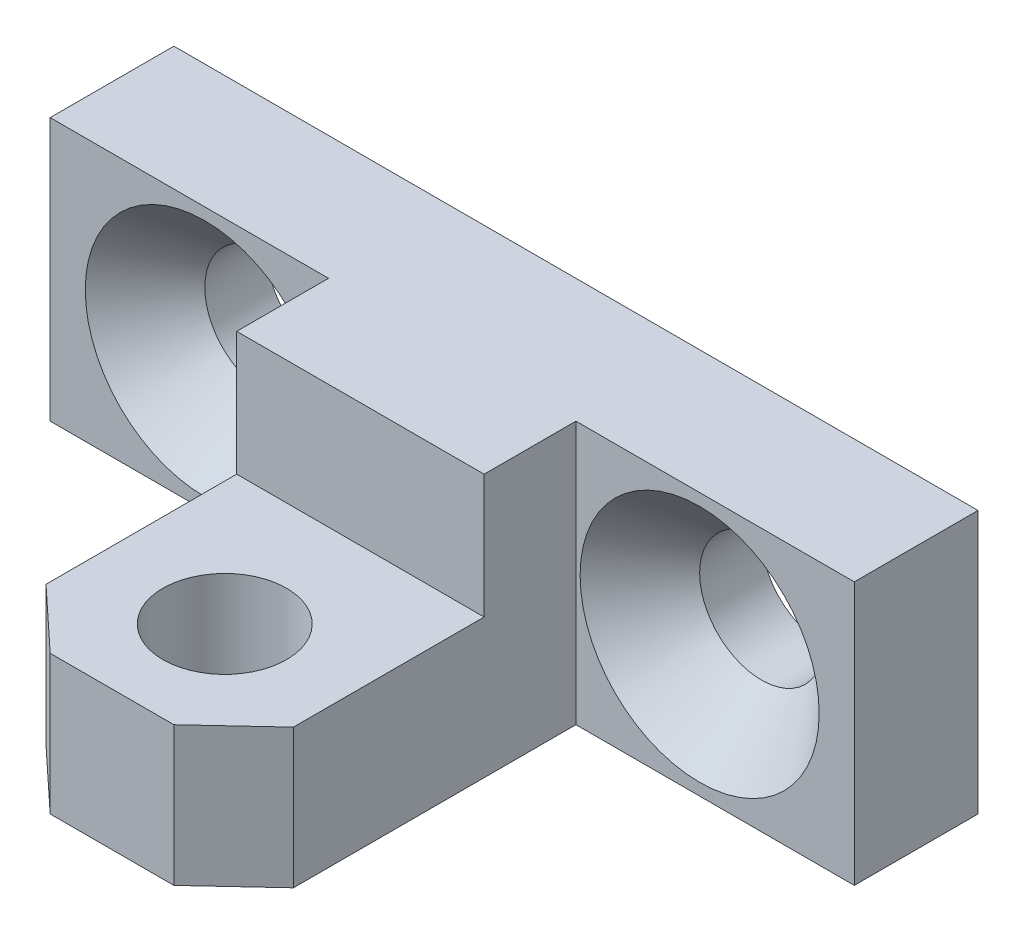
SolidWorks part; units mm, degrees
ref_plane "Спереди" through (0, 0, 0) normal (0, 0, 1) x (1, 0, 0)
ref_plane "Сверху" through (0, 0, 0) normal (0, 1, 0) x (1, 0, 0)
ref_plane "Справа" through (0, 0, 0) normal (1, 0, 0) x (0, 0, -1)
sketch "Эскиз1" plane through (0, 0, 0) normal (0, 0, 1) x (1, 0, 0)
  line L1 (0, 0) -> (26, 0)
  line L2 (0, 0) -> (0, -8.5)
  line L3 (0, -8.5) -> (26, -8.5)
  line L4 (26, 0) -> (26, -8.5)
extrude "Вытянуть1" add sketch "Эскиз1" along normal blind 15
sketch "Эскиз2" plane through (0, 0, 0) normal (0, 1, 0) x (1, 0, 0)
  line L0 (13, 0) -> (13, 9.2119) construction
  line L2 (0, -15) -> (0, 0) construction
  line L3 (0, -4) -> (9, -4)
  line L4 (0, -4) -> (0, -21.1515)
  line L5 (0, -21.1515) -> (9, -21.1515)
  line L6 (9, -4) -> (9, -21.1515)
  line L7 (26, 0) -> (0, 0) construction
  line L8 (17, -4) -> (17, -21.1515)
  line L9 (26, -21.1515) -> (17, -21.1515)
  line L10 (26, -4) -> (26, -21.1515)
  line L11 (26, -4) -> (17, -4)
  dimension "D1" = 4
extrude "Вытянуть2" cut sketch "Эскиз2" against normal blind 20
chamfer "Фаска1" distance 2 angle 43 2 edges at (17, -4.25, 15) (9, -4.25, 15) first distance on face at (13, -4.25, 15)
sketch "Эскиз3" plane through (0, 0, 0) normal (0, 0, -1) x (-1, 0, 0)
  circle A0 centre (-21, -4.25) radius 2
  circle A1 centre (-5, -4.2515) radius 2
extrude "Вырез-Вытянуть1" cut sketch "Эскиз3" against normal through all
chamfer "Фаска2" distance 2 angle 43 2 edges at (19, -4.25, 4) (3, -4.2515, 4) first distance on face at (19, -4.25, 0) first distance on face at (3, -4.2515, 0)
sketch "Эскиз4" plane through (0, 0, 0) normal (0, 1, 0) x (1, 0, 0)
  line L1 (7.3896, -6.9688) -> (18.7368, -6.9688)
  line L2 (7.3896, -6.9688) -> (7.3896, -15.8517)
  line L3 (7.3896, -15.8517) -> (18.7368, -15.8517)
  line L4 (18.7368, -6.9688) -> (18.7368, -15.8517)
extrude "Вырез-Вытянуть2" cut sketch "Эскиз4" against normal blind 4
sketch "Эскиз5" plane through (0, -4, 0) normal (0, 1, 0) x (1, 0, 0)
  circle A0 centre (13, -11.3557) radius 2
extrude "Вырез-Вытянуть3" cut sketch "Эскиз5" against normal through all
